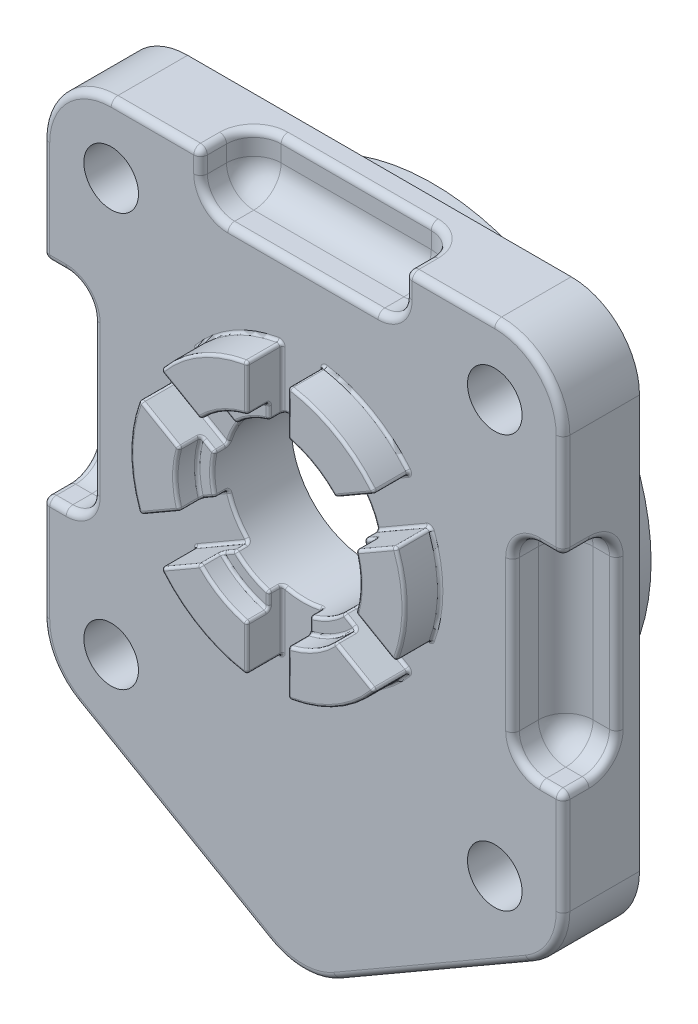
SolidWorks part; units mm, degrees
note: The reader was unsure of these and kept them because the rebuilt part matched: shared geometry of "Sketch3<3>", "Sketch3<4>", "Sketch3<5>", "Sketch4<5>".
material "1023 Carbon Steel Sheet (SS)"
ref_plane "Front Plane" through (0, 0, 0) normal (0, 0, 1) x (1, 0, 0)
ref_plane "Top Plane" through (0, 0, 0) normal (0, 1, 0) x (1, 0, 0)
ref_plane "Right Plane" through (0, 0, 0) normal (1, 0, 0) x (0, 0, -1)
sketch "Sketch1" plane through (0, 0, 0) normal (0, 0, 1) x (1, 0, 0)
  line L0 (0, 0) -> (48.387, 0) construction
  line L1 (48.387, 3.6662) -> (48.387, 42.037)
  line L2 (42.037, 48.387) -> (6.35, 48.387)
  line L3 (0, 42.037) -> (0, 3.6662)
  line L4 (3.175, -1.8331) -> (21.0185, -12.135)
  line L5 (27.3685, -12.135) -> (45.212, -1.8331)
  arc A0 (0, 3.6662) -> (3.175, -1.8331) centre (6.35, 3.6662) ccw
  arc A1 (21.0185, -12.135) -> (27.3685, -12.135) centre (24.1935, -6.6358) ccw
  arc A2 (45.212, -1.8331) -> (48.387, 3.6662) centre (42.037, 3.6662) ccw
  arc A3 (48.387, 42.037) -> (42.037, 48.387) centre (42.037, 42.037) ccw
  arc A4 (6.35, 48.387) -> (0, 42.037) centre (6.35, 42.037) ccw
  circle A5 centre (6.35, 42.037) radius 2.54
  circle A6 centre (42.037, 42.037) radius 2.54
  circle A7 centre (42.037, 3.6662) radius 2.54
  circle A8 centre (6.35, 3.6662) radius 2.54
  point P16 (48.387, 48.387)
  dimension "D5" = 6.35
  dimension "D6" = 5.08
  dimension "D1" = 48.387
  dimension "D2" = 48.387
  dimension "D3" = 30
  dimension "D4" = 30
extrude "Boss-Extrude1" add sketch "Sketch1" along normal blind 7.112
sketch "Sketch2" plane through (0, 0, 0) normal (0, 0, 1) x (1, 0, 0)
  line L0 (42.037, 48.387) -> (6.35, 48.387) construction
  line L1 (48.387, 3.6662) -> (48.387, 42.037) construction
  circle A0 centre (24.1935, 24.1935) radius 20.32
  point P2 (24.1935, 48.387)
  dimension "D1" = 40.64
  dimension "D2" = 24.1935
  dimension "D3" = 24.1935
extrude "Boss-Extrude2" add sketch "Sketch2" against normal blind 4.953
ref_plane "Plane1" through (0, 0, -4.953) normal (0, 0, 1) x (1, 0, 0)
sketch "Sketch3" plane through (0, 0, -4.953) normal (0, 0, 1) x (1, 0, 0)
  circle A1 centre (24.1935, 24.1935) radius 17.907
  circle A2 centre (24.1935, 24.1935) radius 13.335
  circle A3 centre (24.1935, 24.1935) radius 7.1755
  circle A4 centre (24.1935, 24.1935) radius 11.1125
  dimension "D1" = 14.351
  dimension "D2" = 22.225
  dimension "D3" = 26.67
  dimension "D4" = 35.814
extrude "Cut-Extrude1" cut sketch "Sketch3" along normal blind 8.636 contours A1 A2
extrude "Cut-Extrude2" cut sketch "Sketch3<3>" along normal blind 7.493 contours A2 A4
sketch "Sketch3<3>" plane through (0, 0, -4.953) normal (0, 0, 1) x (1, 0, 0) same geometry as "Sketch3"
extrude "Cut-Extrude3" cut sketch "Sketch3<4>" along normal through all contours A3
sketch "Sketch3<4>" plane through (0, 0, -4.953) normal (0, 0, 1) x (1, 0, 0) same geometry as "Sketch3"
extrude "Cut-Extrude4" cut sketch "Sketch3<5>" along normal blind 5.969 contours A4 A3
sketch "Sketch3<5>" plane through (0, 0, -4.953) normal (0, 0, 1) x (1, 0, 0) same geometry as "Sketch3"
chamfer "Chamfer1" distance 1.27 angle 41 1 edges at (37.5285, 24.1935, 2.54)
chamfer "Chamfer2" distance 0.508 angle 71 1 edges at (35.306, 24.1935, 1.016)
ref_plane "Plane2" through (0, 0, 7.112) normal (0, 0, 1) x (1, 0, 0)
sketch "Sketch4" plane through (0, 0, 7.112) normal (0, 0, 1) x (1, 0, 0)
  line L5 (24.1935, 24.1935) -> (24.1935, 27.3643) construction
  line L6 (24.1935, 24.1935) -> (29.9004, 24.1935) construction
  circle A0 centre (24.1935, 24.1935) radius 12.7635
  circle A1 centre (24.1935, 24.1935) radius 7.1755
  circle A2 centre (24.1935, 24.1935) radius 8.5725
  dimension "D1" = 25.527
  dimension "D2" = 14.351
  dimension "D3" = 17.145
extrude "Boss-Extrude3" add sketch "Sketch4" along normal blind 3.302 contours A0 A2
extrude "Boss-Extrude5" add sketch "Sketch4<5>" along normal blind 1.27 contours A2 A1
sketch "Sketch4<5>" plane through (0, 0, 7.112) normal (0, 0, 1) x (1, 0, 0) same geometry as "Sketch4"
ref_plane "Plane3" through (0, 0, 10.414) normal (0, 0, 1) x (1, 0, 0)
sketch "Sketch5" plane through (0, 0, 10.414) normal (0, 0, 1) x (1, 0, 0)
  line L0 (24.1935, 24.1935) -> (24.1935, 28.3446) construction
  line L1 (24.1935, 24.1935) -> (29.1582, 24.1935) construction
  line L2 (26.0985, 24.1935) -> (26.0985, 40.7035)
  line L3 (26.0985, 40.7035) -> (22.2885, 40.7035)
  line L4 (22.2885, 40.7035) -> (22.2885, 7.6835)
  line L5 (22.2885, 7.6835) -> (26.0985, 7.6835)
  line L6 (26.0985, 7.6835) -> (26.0985, 24.1935)
  line L7 (39.4456, 17.5891) -> (10.8494, 34.0991)
  line L8 (37.5406, 14.2896) -> (39.4456, 17.5891)
  line L9 (23.2425, 22.5446) -> (37.5406, 14.2896)
  line L10 (8.9444, 30.7996) -> (23.2425, 22.5446)
  line L11 (10.8494, 34.0991) -> (8.9444, 30.7996)
  line L12 (10.8494, 14.2879) -> (39.4456, 30.7979)
  line L13 (8.9444, 17.5874) -> (10.8494, 14.2879)
  line L14 (23.2425, 25.8424) -> (8.9444, 17.5874)
  line L15 (37.5406, 34.0974) -> (23.2425, 25.8424)
  line L16 (39.4456, 30.7979) -> (37.5406, 34.0974)
  dimension "D1" = 3
  dimension "D2" = 3.81
  dimension "D3" = 33.02
extrude "Cut-Extrude5" cut sketch "Sketch5" against normal blind 3.302
fillet "Fillet1" radius 0.254 108 edges at (19.9079, 31.6179, 10.414) (19.9079, 16.7691, 10.414) (22.2885, 34.6828, 10.414) (22.2885, 13.7042, 10.414) (26.0985, 34.6828, 10.414) (28.4804, 31.6171, 10.414) (17.8124, 35.2474, 10.414) (17.8124, 13.1396, 10.414) (30.5759, 13.1404, 10.414) (30.5759, 35.2466, 10.414) (24.1935, 31.369, 7.112) (24.1935, 17.018, 7.112) (26.0985, 32.5517, 9.398) (22.2885, 32.5517, 9.398) (22.2885, 15.8353, 9.398) (22.2885, 17.2755, 7.747) (22.2885, 31.1115, 7.747) (26.0985, 31.1115, 7.747) (17.8124, 35.2474, 7.112) (17.8124, 13.1396, 7.112) (19.9079, 31.6179, 8.382) (19.9079, 16.7691, 8.382) (20.6064, 17.9789, 8.382) (20.6064, 30.4081, 8.382) (22.2885, 31.8316, 8.382) (22.2885, 16.5554, 8.382) (22.2885, 36.814, 8.763) (22.2885, 11.573, 8.763) (22.2885, 33.9628, 7.112) (22.2885, 14.4242, 7.112) (26.0985, 17.2755, 7.747) (26.0985, 16.5554, 8.382) (26.0985, 15.8353, 9.398) (26.0985, 13.7042, 10.414) (26.0985, 14.4242, 7.112) (26.0985, 11.573, 8.763) (28.4804, 16.7699, 10.414) (28.4804, 16.7699, 8.382) (27.7819, 17.9797, 8.382) (30.5759, 13.1404, 7.112) (26.0985, 36.814, 8.763) (26.0985, 33.9628, 7.112) (30.5759, 35.2466, 7.112) (27.7819, 30.4073, 8.382) (26.0985, 31.8316, 8.382) (28.4804, 31.6171, 8.382) (29.2333, 19.0858, 7.747) (19.1559, 19.0836, 7.747) (31.1376, 26.0012, 7.747) (31.1376, 22.3858, 7.747) (19.1559, 29.3034, 7.747) (31.7612, 26.3613, 8.382) (18.5323, 18.7236, 8.382) (32.3848, 26.7213, 9.398) (17.9087, 18.3635, 9.398) (29.8568, 18.7258, 8.382) (31.7025, 17.6602, 7.112) (17.9801, 20.6044, 7.112) (33.6069, 27.4269, 7.112) (16.6866, 17.6579, 7.112) (32.3848, 21.6657, 9.398) (17.9087, 30.0235, 9.398) (29.2333, 29.3012, 7.747) (33.6069, 20.9601, 7.112) (16.6866, 30.7291, 7.112) (29.8568, 29.6612, 8.382) (17.2502, 26.0042, 7.747) (16.0031, 26.7243, 9.398) (30.4804, 18.3658, 9.398) (34.1717, 16.2346, 8.763) (36.0763, 19.5344, 8.763) (14.2172, 32.1547, 8.763) (17.2502, 22.3828, 7.747) (16.6267, 22.0228, 8.382) (16.0031, 21.6627, 9.398) (36.0763, 28.8526, 8.763) (14.2172, 16.2323, 8.763) (34.2305, 27.787, 10.414) (16.063, 17.2979, 10.414) (14.781, 20.9572, 7.112) (12.3118, 19.5316, 8.763) (14.1575, 20.5972, 10.414) (12.3118, 28.8554, 8.763) (11.43, 24.1935, 7.112) (31.7612, 22.0257, 8.382) (18.5323, 29.6634, 8.382) (11.43, 24.1935, 10.414) (32.326, 17.3002, 10.414) (30.4084, 27.7799, 7.112) (30.4084, 20.6071, 7.112) (31.369, 24.1935, 8.382) (34.2305, 20.6, 10.414) (16.063, 31.0891, 10.414) (32.766, 24.1935, 8.382) (32.766, 24.1935, 10.414) (36.957, 24.1935, 7.112) (36.957, 24.1935, 10.414) (30.4804, 30.0212, 9.398) (34.1717, 32.1524, 8.763) (17.9801, 27.7826, 7.112) (14.781, 27.4298, 7.112) (17.018, 24.1935, 8.382) (15.621, 24.1935, 8.382) (15.621, 24.1935, 10.414) (31.7025, 30.7268, 7.112) (32.326, 31.0868, 10.414) (16.6267, 26.3642, 8.382) (14.1575, 27.7898, 10.414)
sketch "Sketch6" plane through (0, 0, 7.112) normal (0, 0, 1) x (1, 0, 0)
  line L0 (0, 13.3266) -> (0, 32.3766)
  line L1 (0, 42.037) -> (0, 3.6662) construction
  line L2 (0, 32.3766) -> (2.159, 32.3766)
  line L3 (4.699, 29.8366) -> (4.699, 15.8666)
  line L4 (2.159, 13.3266) -> (0, 13.3266)
  line L5 (24.1935, 48.387) -> (24.1935, 65.5127) construction
  line L6 (42.037, 48.387) -> (6.35, 48.387) construction
  line L7 (48.387, 13.3266) -> (48.387, 32.3766)
  line L8 (46.228, 13.3266) -> (48.387, 13.3266)
  line L9 (43.688, 29.8366) -> (43.688, 15.8666)
  line L10 (48.387, 32.3766) -> (46.228, 32.3766)
  line L11 (14.6685, 48.387) -> (33.7185, 48.387)
  line L12 (33.7185, 48.387) -> (33.7185, 46.228)
  line L13 (31.1785, 43.688) -> (17.2085, 43.688)
  line L14 (14.6685, 46.228) -> (14.6685, 48.387)
  arc A0 (2.159, 13.3266) -> (4.699, 15.8666) centre (2.159, 15.8666) ccw
  arc A1 (4.699, 29.8366) -> (2.159, 32.3766) centre (2.159, 29.8366) ccw
  arc A2 (46.228, 13.3266) -> (43.688, 15.8666) centre (46.228, 15.8666) cw
  arc A3 (43.688, 29.8366) -> (46.228, 32.3766) centre (46.228, 29.8366) cw
  arc A4 (33.7185, 46.228) -> (31.1785, 43.688) centre (31.1785, 46.228) cw
  arc A5 (17.2085, 43.688) -> (14.6685, 46.228) centre (17.2085, 46.228) cw
  point P10 (4.699, 32.3766)
  dimension "D3" = 2.54
  dimension "D5" = 2.54
  dimension "D1" = 4.699
  dimension "D2" = 19.05
  dimension "D4" = 9.6604
  dimension "D6" = 4.699
extrude "Cut-Extrude6" cut sketch "Sketch6" against normal blind 4.953
fillet "Fillet2" radius 2.54 15 edges at (1.0795, 13.3266, 2.159) (3.9551, 14.0705, 2.159) (1.0795, 32.3766, 2.159) (3.9551, 31.6326, 2.159) (4.699, 22.8516, 2.159) (47.3075, 32.3766, 2.159) (44.4319, 31.6326, 2.159) (47.3075, 13.3266, 2.159) (44.4319, 14.0705, 2.159) (43.688, 22.8516, 2.159) (14.6685, 47.3075, 2.159) (15.4124, 44.4319, 2.159) (33.7185, 47.3075, 2.159) (32.9746, 44.4319, 2.159) (24.1935, 43.688, 2.159)
fillet "Fillet3" radius 0.635 43 edges at (1.0795, 13.3266, 7.112) (3.9551, 14.0705, 7.112) (1.0795, 32.3766, 7.112) (3.9551, 31.6326, 7.112) (0, 32.3766, 5.9055) (0, 31.6326, 2.9029) (0, 13.3266, 5.9055) (0, 14.0705, 2.9029) (0, 8.4964, 7.112) (0.8507, 0.4912, 7.112) (12.0967, -6.9841, 7.112) (24.1935, -12.9858, 7.112) (36.2903, -6.9841, 7.112) (47.5363, 0.4912, 7.112) (48.387, 13.3266, 5.9055) (48.387, 14.0705, 2.9029) (48.387, 32.3766, 5.9055) (48.387, 31.6326, 2.9029) (47.3075, 32.3766, 7.112) (44.4319, 31.6326, 7.112) (47.3075, 13.3266, 7.112) (44.4319, 14.0705, 7.112) (48.387, 37.2068, 7.112) (46.5271, 46.5271, 7.112) (33.7185, 48.387, 5.9055) (32.9746, 48.387, 2.9029) (14.6685, 48.387, 5.9055) (15.4124, 48.387, 2.9029) (33.7185, 47.3075, 7.112) (32.9746, 44.4319, 7.112) (24.1935, 43.688, 7.112) (15.4124, 44.4319, 7.112) (0, 37.2068, 7.112) (1.8599, 46.5271, 7.112) (4.699, 22.8516, 7.112) (0, 22.8516, 2.159) (48.387, 8.4964, 7.112) (48.387, 22.8516, 2.159) (43.688, 22.8516, 7.112) (37.8777, 48.387, 7.112) (24.1935, 48.387, 2.159) (14.6685, 47.3075, 7.112) (10.5093, 48.387, 7.112)
sketch "Sketch8" plane through (0, 0, 0) normal (0, 0, 1) x (1, 0, 0)
  line L0 (0, 0) -> (0, -11.6338) construction
  line L1 (0, 0) -> (-11.5366, 0) construction
  circle A0 centre (24.1935, -6.6358) radius 0.889
ref_plane "Plane5" through (24.1935, 0, 0) normal (1, 0, 0) x (0, 0, -1)
sketch "Sketch9" plane through (24.1935, 0, 0) normal (1, 0, 0) x (0, 0, -1)
  line L0 (-3.683, 6.2865) -> (-3.048, 6.2865)
  line L1 (-3.683, 6.2865) -> (4.953, 6.2865) construction
  line L2 (-3.048, 6.2865) -> (0, -6.6224)
ref_plane "Plane6" through (0, 4.9507, 0) normal (0, 1, 0) x (-1, 0, 0)
extrude "Cut-Extrude7" cut sketch "Sketch8" along direction (0, -0.9732, -0.2298) on the side of the normal blind 6.35
